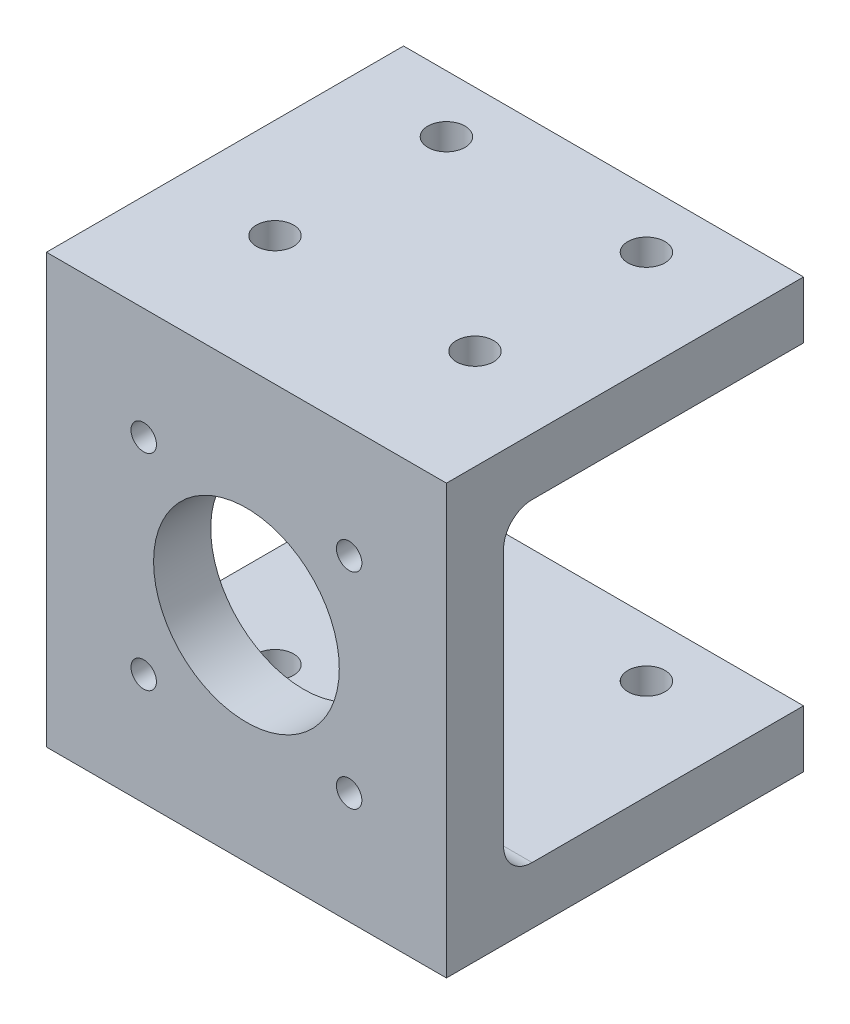
SolidWorks part; units mm, degrees
material "ABS"
ref_plane "Front Plane" through (0, 0, 0) normal (0, 0, 1) x (1, 0, 0)
ref_plane "Top Plane" through (0, 0, 0) normal (0, 1, 0) x (1, 0, 0)
ref_plane "Right Plane" through (0, 0, 0) normal (1, 0, 0) x (0, 0, -1)
sketch "Sketch1" plane through (0, 0, 0) normal (0, 0, 1) x (1, 0, 0)
  line L1 (-17.78, -19.05) -> (17.78, -19.05)
  line L2 (-17.78, -19.05) -> (-17.78, 19.05)
  line L3 (-17.78, 19.05) -> (17.78, 19.05)
  line L4 (17.78, -19.05) -> (17.78, 19.05)
  line L5 (-17.78, -19.05) -> (17.78, 19.05) construction
  line L6 (-17.78, 19.05) -> (17.78, -19.05) construction
  line L7 (-9.1313, -9.1313) -> (9.1313, -9.1313) construction
  line L8 (-9.1313, -9.1313) -> (-9.1313, 9.1313) construction
  line L9 (-9.1313, 9.1313) -> (9.1313, 9.1313) construction
  line L10 (9.1313, -9.1313) -> (9.1313, 9.1313) construction
  line L11 (-9.1313, -9.1313) -> (9.1313, 9.1313) construction
  line L12 (-9.1313, 9.1313) -> (9.1313, -9.1313) construction
  circle A0 centre (0, 0) radius 8.255
  circle A1 centre (-9.1313, 9.1313) radius 1.1303
  circle A2 centre (9.1313, 9.1313) radius 1.1303
  circle A3 centre (-9.1313, -9.1313) radius 1.1303
  circle A4 centre (9.1313, -9.1313) radius 1.1303
  point P0 (0, 0)
  dimension "D3" = 16.51
  dimension "D5" = 2.2606
  dimension "D1" = 38.1
  dimension "D2" = 35.56
  dimension "D4" = 18.2626
  dimension "D6" = 18.2626
extrude "Boss-Extrude with 4-40 Tap Drill Holes" add sketch "Sketch1" against normal mid plane 31.75
sketch "Sketch3" plane through (17.78, 0, 0) normal (1, 0, 0) x (0, 0, -1)
  line L0 (15.875, -19.05) -> (15.875, 19.05) construction
  line L1 (15.875, 13.97) -> (-10.795, 13.97)
  line L2 (15.875, 13.97) -> (15.875, -13.97)
  line L3 (15.875, -13.97) -> (-10.795, -13.97)
  line L4 (-10.795, 13.97) -> (-10.795, -13.97)
  line L5 (15.875, 19.05) -> (-15.875, 19.05) construction
  line L6 (15.875, -19.05) -> (-15.875, -19.05) construction
  line L7 (-15.875, -19.05) -> (-15.875, 19.05) construction
  dimension "D1" = 5.08
  dimension "D2" = 5.08
  dimension "D3" = 5.08
extrude "Cut-Extrude1" cut sketch "Sketch3" against normal up to next
fillet "Fillet1" radius 2.54 2 edges at (0, -13.97, 10.795) (0, 13.97, 10.795)
sketch "Sketch5" plane through (0, 19.05, 0) normal (0, 1, 0) x (1, 0, 0)
  line L4 (-17.78, 15.875) -> (-17.78, -8.255)
  line L5 (-17.78, 15.875) -> (-17.78, -8.255)
  line L6 (17.78, -8.255) -> (17.78, 15.875)
  line L7 (17.78, 15.875) -> (-17.78, 15.875)
  line L8 (-17.78, -8.255) -> (17.78, -8.255)
  line L9 (-17.78, -8.255) -> (17.78, -8.255)
  line L10 (17.78, -8.255) -> (17.78, 15.875)
  line L11 (17.78, 15.875) -> (-17.78, 15.875)
  circle A0 centre (-8.89, 10.795) radius 1.65
  circle A1 centre (8.89, 10.795) radius 1.65
  circle A2 centre (8.89, -4.445) radius 1.65
  circle A3 centre (-8.89, -4.445) radius 1.65
  dimension "D2" = 3.3
  dimension "D3" = 8.89
  dimension "D4" = 8.89
  dimension "D5" = 5.08
  dimension "D6" = 3.81
  dimension "D1" = 0
extrude "Clearance Holes for M3 Screw" cut sketch "Sketch5" against normal through all contours A0 | A3 | A2 | A1 region at (-8.89, 19.05, -10.795) region at (8.89, 19.05, -10.795) region at (8.89, 19.05, 4.445) region at (-8.89, 19.05, 4.445)
